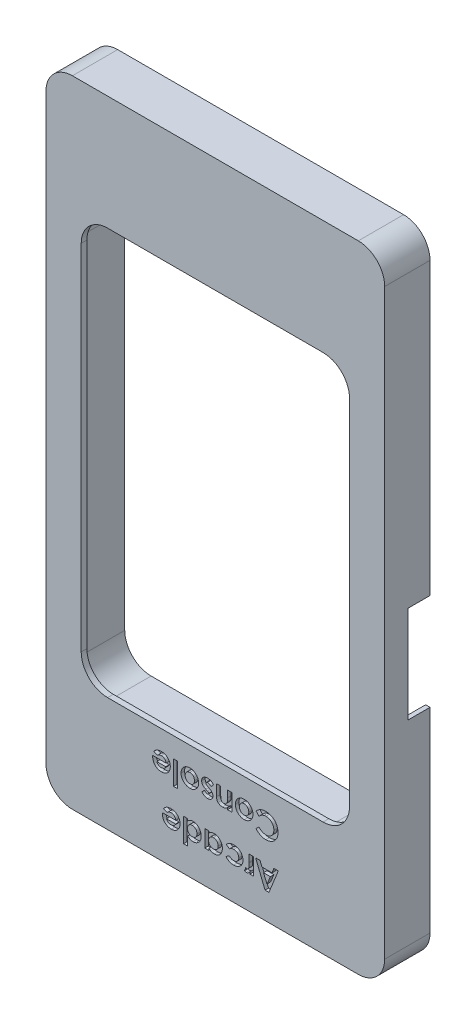
SolidWorks part; units mm, degrees
ref_plane "Ebene vorne" through (0, 0, 0) normal (1, 0, 0) x (0, 1, 0)
ref_plane "Ebene oben" through (0, 0, 0) normal (0, 0, 1) x (0, 1, 0)
ref_plane "Ebene rechts" through (0, 0, 0) normal (0, 1, 0) x (-1, 0, 0)
sketch "DiplayCase" plane through (0, 0, 0) normal (0, 0, 1) x (0, 1, 0)
  line L1 (-46.22, -30.5) -> (46.22, -30.5)
  line L2 (-46.22, -30.5) -> (-46.22, 30.5)
  line L3 (-46.22, 30.5) -> (46.22, 30.5)
  line L4 (46.22, -30.5) -> (46.22, 30.5)
  line L5 (-46.22, -30.5) -> (46.22, 30.5) construction
  line L6 (-46.22, 30.5) -> (46.22, -30.5) construction
  line L7 (-72.22, -38.5) -> (72.22, -38.5)
  line L8 (-72.22, -38.5) -> (-72.22, 38.5)
  line L9 (-72.22, 38.5) -> (72.22, 38.5)
  line L10 (72.22, -38.5) -> (72.22, 38.5)
  line L11 (-72.22, -38.5) -> (72.22, 38.5) construction
  line L12 (-72.22, 38.5) -> (72.22, -38.5) construction
  point P0 (0, 0)
  point P6 (0, 0)
  dimension "D1" = 61
  dimension "D2" = 92.44
  dimension "D3" = 8
  dimension "D4" = 26
extrude "UpperCase" add sketch "DiplayCase" along normal blind 10.3
fillet "Verrundung1" radius 6 4 edges at (30.5, 46.22, 5.15) (-30.5, 46.22, 5.15) (30.5, -46.22, 5.15) (-30.5, -46.22, 5.15)
sketch "Skizze2" plane through (0, 0, 0) normal (0, 0, -1) x (1, 0, 0)
  line L1 (-30.9, -47.32) -> (30.9, -47.32)
  line L2 (-30.9, -47.32) -> (-30.9, 47.32)
  line L3 (-30.9, 47.32) -> (30.9, 47.32)
  line L4 (30.9, -47.32) -> (30.9, 47.32)
  line L5 (-30.9, -47.32) -> (30.9, 47.32) construction
  line L6 (-30.9, 47.32) -> (30.9, -47.32) construction
  point P0 (0, 0)
  dimension "D1" = 61.8
  dimension "D2" = 94.64
extrude "Schnitt-Linear austragen1" cut sketch "Skizze2" against normal blind 9
fillet "Verrundung2" radius 6 4 edges at (38.5, -72.22, 5.15) (-38.5, -72.22, 5.15) (38.5, 72.22, 5.15) (-38.5, 72.22, 5.15)
fillet "Verrundung3" radius 6 4 edges at (-30.9, 47.32, 4.5) (30.9, 47.32, 4.5) (30.9, -47.32, 4.5) (-30.9, -47.32, 4.5)
shell "Wandung2" thickness 1 removed face at (0, 0, 0)
sketch "Skizze8" plane through (0, 0, 10.3) normal (0, 0, 1) x (0, -1, 0)
  line L0 (46.22, 0) -> (72.22, 0) construction
  line L1 (46.22, -24.5) -> (46.22, 24.5) construction
  line L2 (72.22, -32.5) -> (72.22, 32.5) construction
  line L3 (60.9348, 18.5) -> (60.9348, -18.5) construction
  text T0 "Arcade \r\nConsole" font "Century Gothic" height in points 20
  point P10 (60.9348, 0)
extrude "Text_ArcadeConsole" cut sketch "Skizze8" against normal blind 0.8
sketch "Skizze11" plane through (0, 47.32, 0) normal (0, -1, 0) x (1, 0, 0)
  line L1 (-10.85, -4.17) -> (10.85, -4.17)
  line L2 (-10.85, -4.17) -> (-10.85, 4.17)
  line L3 (-10.85, 4.17) -> (10.85, 4.17)
  line L4 (10.85, -4.17) -> (10.85, 4.17)
  line L5 (-10.85, -4.17) -> (10.85, 4.17) construction
  line L6 (-10.85, 4.17) -> (10.85, -4.17) construction
  point P0 (0, 0)
  dimension "D1" = 21.7
  dimension "D2" = 8.34
extrude "Hole_DisplayCables" cut sketch "Skizze11" against normal blind 1
sketch "Skizze12" plane through (0, 0, 9.3) normal (0, 0, -1) x (1, 0, 0)
  line L1 (-31.5, -66) -> (31.5, -66) construction
  line L2 (-31.5, -66) -> (-31.5, 66) construction
  line L3 (-31.5, 66) -> (31.5, 66) construction
  line L4 (31.5, -66) -> (31.5, 66) construction
  line L5 (-31.5, -66) -> (31.5, 66) construction
  line L6 (-31.5, 66) -> (31.5, -66) construction
  circle A2 centre (34, 68) radius 2.5
  circle A3 centre (34, 68) radius 1.25
  circle A4 centre (-34, 68) radius 2.5
  circle A5 centre (-34, 68) radius 1.25
  circle A6 centre (34, -68) radius 2.5
  circle A7 centre (34, -68) radius 1.25
  circle A8 centre (-34, -68) radius 2.5
  circle A9 centre (-34, -68) radius 1.25
  point P0 (0, 0)
  dimension "D3" = 5
  dimension "D4" = 2.5
  dimension "D6" = 2.5
  dimension "D7" = 5
  dimension "D8" = 2.5
  dimension "D11" = 5
  dimension "D12" = 2.5
  dimension "D15" = 5
  dimension "D16" = 2.5
  dimension "D1" = 63
  dimension "D2" = 132
  dimension "D5" = 2
  dimension "D9" = 2.5
  dimension "D10" = 2
  dimension "D13" = 2.5
  dimension "D14" = 2
extrude "Aufsatz-Linear austragen4" add sketch "Skizze12" along normal blind 4 contours A6 | A7 | A4 | A5 | A3 | A2 | A8 | A9
sketch "Skizze16" plane through (38.5, 0, 0) normal (1, 0, 0) x (0, 1, 0)
  line L0 (-66.22, 0) -> (66.22, 0) construction
  line L2 (0.22, 0) -> (-21.78, 0)
  line L3 (0.22, 0) -> (0.22, 5)
  line L4 (0.22, 5) -> (-21.78, 5)
  line L5 (-21.78, 0) -> (-21.78, 5)
  dimension "D1" = 66
  dimension "D2" = 22
  dimension "D3" = 5
extrude "Schnitt-Linear austragen3" cut sketch "Skizze16" against normal blind 11
